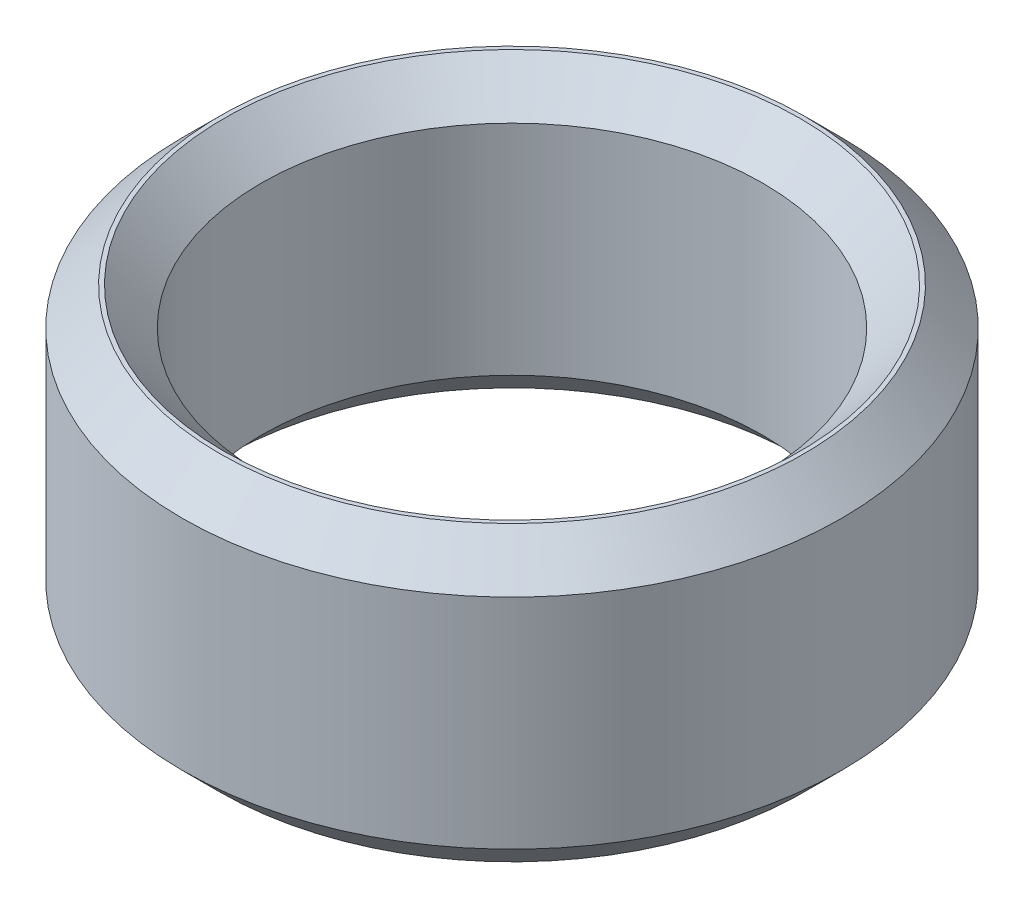
SolidWorks part; units mm, degrees
ref_plane "Front Plane" through (0, 0, 0) normal (0, 0, 1) x (1, 0, 0)
ref_plane "Top Plane" through (0, 0, 0) normal (0, 1, 0) x (1, 0, 0)
ref_plane "Right Plane" through (0, 0, 0) normal (1, 0, 0) x (0, 0, -1)
sketch "Sketch1" plane through (0, 0, 0) normal (0, 1, 0) x (1, 0, 0)
  circle A0 centre (0, 0) radius 12.5
  dimension "SLEEVE_OD" = 25
extrude "Boss-Extrude1" add sketch "Sketch1" along normal blind 11.1093
sketch "Sketch2" plane through (0, 0, 0) normal (0, 1, 0) x (1, 0, 0)
  circle A0 centre (0, 0) radius 9.5102
  dimension "BORE_D" = 19.0205
extrude "Cut-Extrude1" cut sketch "Sketch2" along normal through all
chamfer "Chamfer1" distance 1.4162 angle 45 4 edges at (0, 11.1093, 9.5102) (0, 0, 9.5102) (0, 0, 12.5) (0, 11.1093, 12.5)
